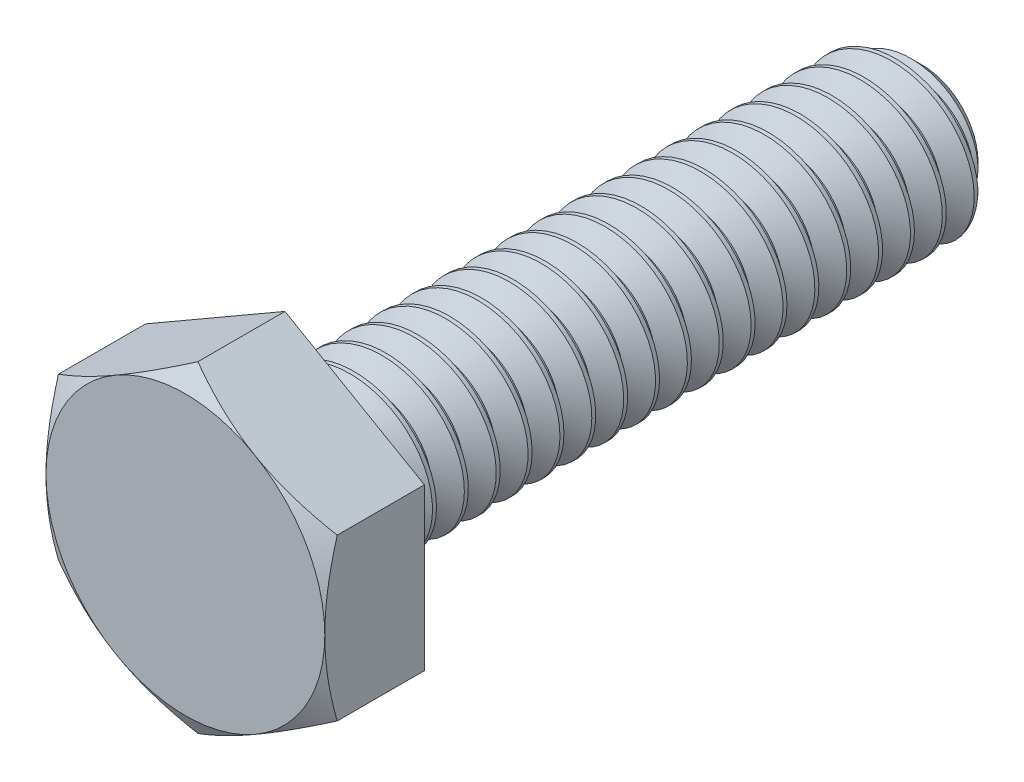
SolidWorks part; units mm, degrees
ref_plane "Front Plane" through (0, 0, 0) normal (0, 0, 1) x (1, 0, 0)
ref_plane "Top Plane" through (0, 0, 0) normal (0, 1, 0) x (1, 0, 0)
ref_plane "Right Plane" through (0, 0, 0) normal (1, 0, 0) x (0, 0, -1)
sketch "Sketch1" plane through (0, 0, 0) normal (1, 0, 0) x (0, 0, -1)
  line L0 (0, 0) -> (25.4, 0) construction
  line L1 (25.4, 3.175) -> (25.4, -3.175) construction
  line L2 (0, 5.5563) -> (0, -5.5563) construction
  line L3 (0, 0) -> (-3.9687, 0) construction
  line L4 (-3.9688, 5.5563) -> (-3.9687, -5.5562) construction
  line L5 (25.3206, 3.3125) -> (26.5906, 3.3125) construction
  line L6 (26.5906, 3.3125) -> (25.9556, 2.2126) construction
  line L7 (25.9556, 2.2126) -> (25.3206, 3.3125) construction
  line L8 (25.3603, 3.2437) -> (26.5509, 3.2437) construction
  line L9 (25.4, 3.175) -> (26.5112, 3.175) construction
  line L10 (25.8762, 2.3501) -> (26.035, 2.3501) construction
  line L11 (25.9556, 3.3125) -> (25.9556, 3.175) construction
  line L12 (25.9556, 2.3501) -> (25.9556, 2.2126) construction
  point P5 (25.4, 0)
  point P9 (0, 0)
  point P13 (-3.9687, 0)
  point P18 (22.225, -3.175)
  point P25 (25.9556, 3.2437)
  dimension "Length" = 25.4
  dimension "Thread OD" = 6.35
  dimension "Hex Width" = 11.1125
  dimension "Hex Height" = 3.9688
  dimension "D1" = 60
  dimension "Pitch" = 1.27
  dimension "D2" = 0.1588
  dimension "D3" = 3.175
sketch "Sketch2" plane through (0, 0, 0) normal (1, 0, 0) x (0, 0, -1)
  line L0 (0, 0) -> (25.4, 0)
  line L1 (0, 5.5563) -> (0, -5.5563) construction
  line L2 (25.4, 0) -> (25.4, 3.175)
  line L3 (25.4, 3.175) -> (0, 3.175)
  line L4 (0, 3.175) -> (0, 0)
revolve "Revolve1" add sketch "Sketch2" angle 360 about L0
sketch "Sketch3" plane through (0, 0, 0) normal (0, 0, 1) x (1, 0, 0)
  line L1 (0, 6.4158) -> (-5.5562, 3.2079)
  line L2 (-5.5562, 3.2079) -> (-5.5562, -3.2079)
  line L3 (-5.5562, -3.2079) -> (0, -6.4158)
  line L4 (0, -6.4158) -> (5.5562, -3.2079)
  line L5 (5.5562, -3.2079) -> (5.5562, 3.2079)
  line L6 (5.5562, 3.2079) -> (0, 6.4158)
  circle A0 centre (0, 0) radius 5.5563 construction
extrude "Boss-Extrude1" add sketch "Sketch3" along normal up to vertex (3.9688 mm away) up to point (0, 0, 3.9687)
chamfer "Chamfer1" distance 0.9525 angle 45 1 edges at (3.175, 0, -25.4)
sketch "Sketch4" plane through (0, 0, 3.9687) normal (0, 0, 1) x (1, 0, 0)
  circle A0 centre (0, 0) radius 5.5563
extrude "Cut-Extrude1" cut sketch "Sketch4" against normal through all draft 60 flip side to cut
ref_axis "Center Axis 1" through (0, 0, -68.7678) along (0, 0, 1)
split "Split1" bodies to split 106 resulting bodies 107 108 split by face at (3.175, 0, 0)
sketch "Sketch5" plane through (0, 0, 0) normal (1, 0, 0) x (0, 0, -1)
  line L0 (25.3603, 3.2437) -> (26.5509, 3.2437)
  line L1 (25.3603, 3.2437) -> (25.8762, 2.3501)
  line L2 (25.8762, 2.3501) -> (26.035, 2.3501)
  line L3 (26.5509, 3.2437) -> (26.035, 2.3501)
sketch "Sketch6" plane through (0, 0, -25.4) normal (0, 0, -1) x (-1, 0, 0)
  circle A0 centre (0, 0) radius 3.175
curve "Helix/Spiral1" pitch 1.27 height 26.67 radius 3.175 centre (0, 0, -25.4) axis (0, 0, 1) start towards (0, 1, 0)
sweep "Cut-Sweep1" cut profiles "Sketch5" path "Helix/Spiral1" align with end faces yes
combine bodies "Combine1" operation type add bodies to combine 108 109
equation "\"D2@Sketch1\"=\"Pitch@Sketch1\"/8"
equation "\"D1@Chamfer1\"=\"Pitch@Sketch1\"*.75"
equation "\"D4@Helix/Spiral1\"=\"Pitch@Sketch1\""
equation "\"D3@Helix/Spiral1\"=\"Length@Sketch1\"+\"Pitch@Sketch1\""
equation "\"D3@Sketch1\"=\"Pitch@Sketch1\"*2.5"
